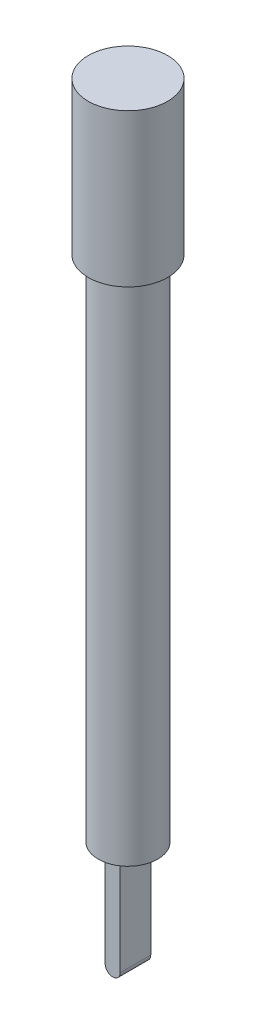
SolidWorks part; units mm, degrees
ref_plane "Front Plane" through (0, 0, 0) normal (0, 0, 1) x (1, 0, 0)
ref_plane "Top Plane" through (0, 0, 0) normal (0, 1, 0) x (1, 0, 0)
ref_plane "Right Plane" through (0, 0, 0) normal (1, 0, 0) x (0, 0, -1)
sketch "Sketch1" plane through (0, 0, 0) normal (0, 1, 0) x (1, 0, 0)
  circle A0 centre (0, 0) radius 5.85
extrude "Boss-Extrude1" add sketch "Sketch1" along normal blind 100
sketch "Sketch2" plane through (0, 100, 0) normal (0, 1, 0) x (1, 0, 0)
  circle A0 centre (0, 0) radius 7.8
extrude "Boss-Extrude2" add sketch "Sketch2" along normal blind 30
sketch "Sketch3" plane through (0, 0, 0) normal (0, 0, 1) x (1, 0, 0)
  line L0 (1.4784, 0) -> (1.4784, -20)
  line L1 (-5.85, 0) -> (5.85, 0) construction
  line L2 (1.4784, -20) -> (-1.4784, -20)
  line L3 (-1.4784, -20) -> (-1.4784, 0)
  line L4 (0, -20) -> (0, 0) construction
  line L5 (-1.4784, 0) -> (1.4784, 0)
  arc A0 (-1.4784, -20) -> (1.4784, -20) centre (0, -20) ccw
  point P0 (0, 0)
  dimension "D1" = 20
extrude "Boss-Extrude3" add sketch "Sketch3" along normal blind 3 and the other way blind 3 contours L4 L2 L0 L5 | L2 L4 L5 L3 | L2 A0 region at (0.7392, -10, 0) region at (0, -20.6274, 0) region at (-0.7392, -10, 0)
